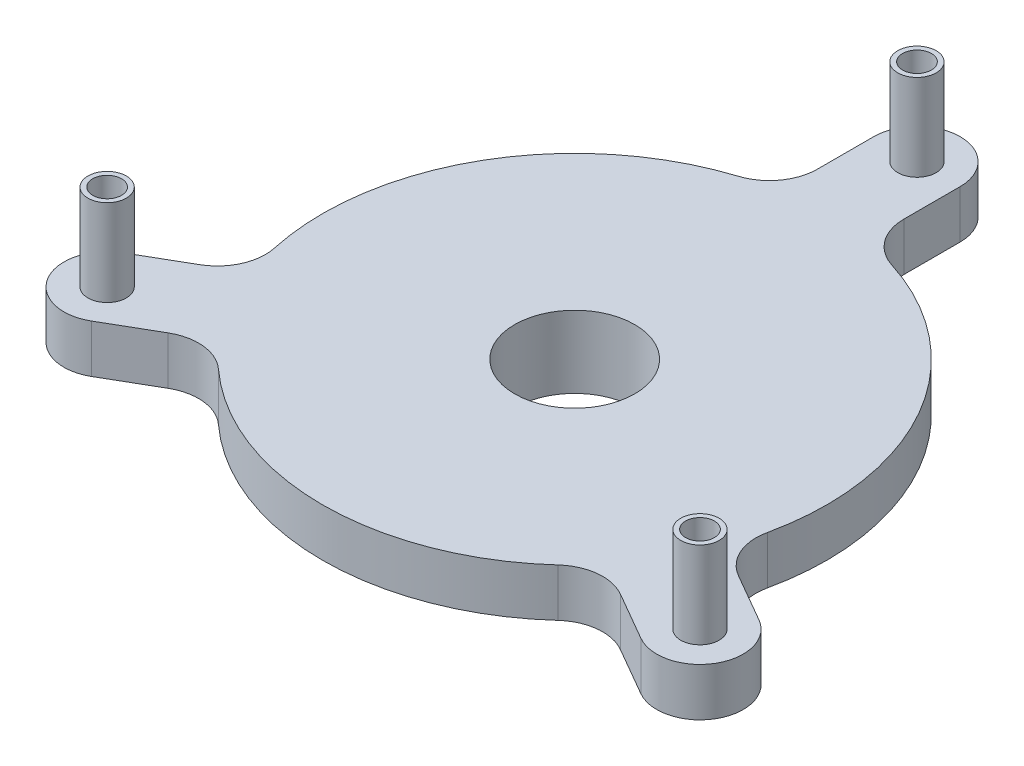
SolidWorks part; units mm, degrees
ref_plane "前基準面" through (0, 0, 0) normal (0, 0, 1) x (1, 0, 0)
ref_plane "上基準面" through (0, 0, 0) normal (0, 1, 0) x (1, 0, 0)
ref_plane "右基準面" through (0, 0, 0) normal (1, 0, 0) x (0, 0, -1)
sketch "草圖1" plane through (0, 0, 0) normal (0, 1, 0) x (1, 0, 0)
  circle A0 centre (0, 0) radius 82.5
  circle A1 centre (0, 0) radius 12.5
  dimension "D1" = 165
  dimension "D2" = 25
extrude "填料-伸長1" add sketch "草圖1" along normal blind 5
sketch "草圖2" plane through (0, 5, 0) normal (0, 1, 0) x (1, 0, 0)
  line L0 (0, 0) -> (0, 82.5) construction
  line L1 (0, 0) -> (71.4471, -41.25) construction
  line L2 (0, 0) -> (-71.4471, -41.25) construction
  circle A0 centre (0, 0) radius 82.5 construction
  circle A1 centre (0, 71.25) radius 4
  circle A2 centre (61.7043, -35.625) radius 4
  circle A3 centre (-61.7043, -35.625) radius 4
  circle A4 centre (0, 71.25) radius 3
  circle A5 centre (61.7043, -35.625) radius 3
  circle A6 centre (-61.7043, -35.625) radius 3
  point P15 (0, 0)
  point P22 (0, 0)
  dimension "D1" = 8
  dimension "D2" = 3
  dimension "D3" = 71.25
  dimension "D4" = 1
  dimension "D5" = 3
extrude "填料-伸長2" add sketch "草圖2" along normal blind 18
sketch "草圖3" plane through (0, 0, 0) normal (0, -1, 0) x (1, 0, 0)
  circle A0 centre (0, 0) radius 12.5 construction
  circle A1 centre (0, 0) radius 12.5
  circle A2 centre (0, 0) radius 35
  dimension "D2" = 70
  dimension "D1" = 22.5
extrude "填料-伸長3" add sketch "草圖3" along normal blind 5
sketch "草圖4" plane through (0, 5, 0) normal (0, 1, 0) x (1, 0, 0)
  line L0 (-9, 71.25) -> (-9, 59.542)
  line L1 (9, 71.25) -> (9, 59.542)
  line L2 (66.2043, -27.8308) -> (56.0649, -21.9768)
  line L3 (57.2043, -43.4192) -> (47.0649, -37.5652)
  line L4 (-57.2043, -43.4192) -> (-47.0649, -37.5652)
  line L5 (-66.2043, -27.8308) -> (-56.0649, -21.9768)
  circle A0 centre (0, 0) radius 52.5 construction
  arc A1 (-15.96, 50.0153) -> (-51.2945, -11.1859) centre (0, 0) ccw
  circle A2 centre (-61.7043, -35.625) radius 9
  arc A3 (-66.2043, -27.8308) -> (-57.2043, -43.4192) centre (-61.7043, -35.625) ccw
  arc A4 (51.2945, -11.1859) -> (15.96, 50.0153) centre (0, 0) ccw
  arc A5 (-47.0649, -37.5652) -> (-35.3345, -38.8294) centre (-42.0649, -46.2255) cw
  arc A6 (47.0649, -37.5652) -> (35.3345, -38.8294) centre (42.0649, -46.2255) ccw
  arc A7 (56.0649, -21.9768) -> (51.2945, -11.1859) centre (61.0649, -13.3165) cw
  arc A8 (9, 59.542) -> (15.96, 50.0153) centre (19, 59.542) ccw
  arc A9 (-9, 59.542) -> (-15.96, 50.0153) centre (-19, 59.542) cw
  arc A10 (-56.0649, -21.9768) -> (-51.2945, -11.1859) centre (-61.0649, -13.3165) ccw
  circle A11 centre (0, 71.25) radius 9
  arc A12 (9, 71.25) -> (-9, 71.25) centre (0, 71.25) ccw
  circle A13 centre (0, 0) radius 12.5 construction
  circle A14 centre (61.7043, -35.625) radius 9
  arc A15 (57.2043, -43.4192) -> (66.2043, -27.8308) centre (61.7043, -35.625) ccw
  circle A16 centre (0, 0) radius 12.5
  arc A17 (-35.3345, -38.8294) -> (35.3345, -38.8294) centre (0, 0) ccw
  circle A18 centre (0, 0) radius 82.5 construction
  circle A19 centre (0, 0) radius 82.5
  point P28 (0, 0)
  point P35 (-9, 51.7228)
  circle M24 centre (0, 0) radius 82.5
  dimension "D7" = 10
  dimension "D5" = 18
  dimension "D1" = 5
  dimension "D2" = 5
  dimension "D3" = 5
  dimension "D4" = 40
  dimension "D6" = 3
extrude "除料-伸長1" cut sketch "草圖4" against normal blind 10 and the other way through all contours A17 A5 L4 A3 L5 A10 A1 A9 L0 A12 L1 A8 A4 A7 L2 A15 L3 A6 M24 region at (-80.1665, 5, 0)
sketch "草圖5" plane through (0, 0, 0) normal (0, -1, 0) x (1, 0, 0)
  line L6 (-47.0649, 37.5652) -> (-57.2043, 43.4192)
  line L7 (-66.2043, 27.8308) -> (-56.0649, 21.9768)
  line L8 (-9, -59.542) -> (-9, -71.25)
  line L9 (9, -71.25) -> (9, -59.542)
  line L10 (56.0649, 21.9768) -> (66.2043, 27.8308)
  line L11 (57.2043, 43.4192) -> (47.0649, 37.5652)
  line L12 (-47.0649, 37.5652) -> (-57.2043, 43.4192)
  line L13 (-66.2043, 27.8308) -> (-56.0649, 21.9768)
  line L14 (-9, -59.542) -> (-9, -71.25)
  line L15 (9, -71.25) -> (9, -59.542)
  line L16 (56.0649, 21.9768) -> (66.2043, 27.8308)
  line L17 (57.2043, 43.4192) -> (47.0649, 37.5652)
  circle A0 centre (0, 0) radius 46
  arc A13 (35.3345, 38.8294) -> (-35.3345, 38.8294) centre (0, 0) ccw
  arc A14 (-47.0649, 37.5652) -> (-35.3345, 38.8294) centre (-42.0649, 46.2255) ccw
  arc A15 (-57.2043, 43.4192) -> (-66.2043, 27.8308) centre (-61.7043, 35.625) ccw
  arc A16 (-51.2945, 11.1859) -> (-56.0649, 21.9768) centre (-61.0649, 13.3165) ccw
  arc A17 (-51.2945, 11.1859) -> (-15.96, -50.0153) centre (0, 0) ccw
  arc A18 (-9, -59.542) -> (-15.96, -50.0153) centre (-19, -59.542) ccw
  arc A19 (-9, -71.25) -> (9, -71.25) centre (0, -71.25) ccw
  arc A20 (15.96, -50.0153) -> (9, -59.542) centre (19, -59.542) ccw
  arc A21 (15.96, -50.0153) -> (51.2945, 11.1859) centre (0, 0) ccw
  arc A22 (56.0649, 21.9768) -> (51.2945, 11.1859) centre (61.0649, 13.3165) ccw
  arc A23 (66.2043, 27.8308) -> (57.2043, 43.4192) centre (61.7043, 35.625) ccw
  arc A24 (35.3345, 38.8294) -> (47.0649, 37.5652) centre (42.0649, 46.2255) ccw
  arc A25 (35.3345, 38.8294) -> (-35.3345, 38.8294) centre (0, 0) ccw
  arc A26 (-47.0649, 37.5652) -> (-35.3345, 38.8294) centre (-42.0649, 46.2255) ccw
  arc A27 (-57.2043, 43.4192) -> (-66.2043, 27.8308) centre (-61.7043, 35.625) ccw
  arc A28 (-51.2945, 11.1859) -> (-56.0649, 21.9768) centre (-61.0649, 13.3165) ccw
  arc A29 (-51.2945, 11.1859) -> (-15.96, -50.0153) centre (0, 0) ccw
  arc A30 (-9, -59.542) -> (-15.96, -50.0153) centre (-19, -59.542) ccw
  arc A31 (-9, -71.25) -> (9, -71.25) centre (0, -71.25) ccw
  arc A32 (15.96, -50.0153) -> (9, -59.542) centre (19, -59.542) ccw
  arc A33 (15.96, -50.0153) -> (51.2945, 11.1859) centre (0, 0) ccw
  arc A34 (56.0649, 21.9768) -> (51.2945, 11.1859) centre (61.0649, 13.3165) ccw
  arc A35 (66.2043, 27.8308) -> (57.2043, 43.4192) centre (61.7043, 35.625) ccw
  arc A36 (35.3345, 38.8294) -> (47.0649, 37.5652) centre (42.0649, 46.2255) ccw
  dimension "D1" = 0
  dimension "D2" = 92
extrude "填料-伸長4" add sketch "草圖5" along normal up to surface (5 mm away) contours A25 A26 L12 A27 L13 A28 A29 A30 L14 A31 L15 A32 A33 A34 L16 A35 L17 A36 up to face at (0, -5, -35)
sketch "草圖6" plane through (0, 0, 0) normal (0, 1, 0) x (1, 0, 0)
  circle A1 centre (0, 0) radius 12.5
  circle A2 centre (0, 0) radius 12.5
  dimension "D1" = 0
extrude "除料-伸長2" cut sketch "草圖6" against normal through all
sketch "草圖7" plane through (0, -5, 0) normal (0, -1, 0) x (1, 0, 0)
  circle A0 centre (0, 0) radius 34.75
  circle A1 centre (0, 0) radius 12.5 construction
  circle A2 centre (0, 0) radius 12.5
  dimension "D1" = 69.5
extrude "填料-伸長5" add sketch "草圖7" along normal blind 5
